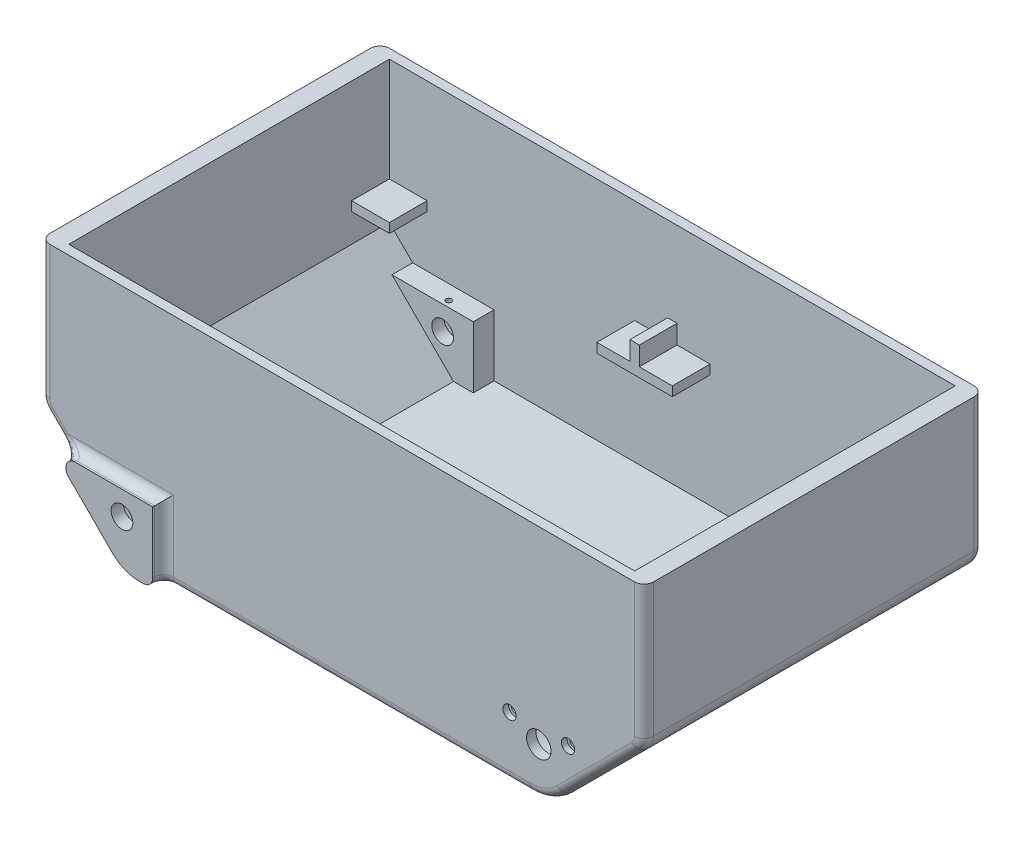
SolidWorks part; units mm, degrees
ref_plane "Front Plane" through (0, 0, 0) normal (0, 0, 1) x (1, 0, 0)
ref_plane "Top Plane" through (0, 0, 0) normal (0, 1, 0) x (1, 0, 0)
ref_plane "Right Plane" through (0, 0, 0) normal (1, 0, 0) x (0, 0, -1)
sketch "Sketch1" plane through (0, 0, 0) normal (0, 1, 0) x (1, 0, 0)
  line L1 (-160, -90) -> (160, -90)
  line L2 (-160, -90) -> (-160, 90)
  line L3 (-160, 90) -> (160, 90)
  line L4 (160, -90) -> (160, 90)
  line L5 (-160, -90) -> (160, 90) construction
  line L6 (-160, 90) -> (160, -90) construction
  point P0 (0, 0)
  dimension "D1" = 320
  dimension "D2" = 180
extrude "Boss-Extrude1" add sketch "Sketch1" along normal blind 50
sketch "Sketch2" plane through (0, 0, 90) normal (0, 0, 1) x (1, 0, 0)
  line L0 (-160, 50) -> (-110, 0)
  line L1 (-160, 0) -> (160, 0) construction
  line L2 (-110, 0) -> (-160, 0)
  line L3 (-160, 0) -> (-160, 50)
  dimension "D1" = 50
extrude "Cut-Extrude2" cut sketch "Sketch2" against normal through all
mirror "Mirror1" about plane through (0, 0, 0) normal (1, 0, 0) of "Cut-Extrude2"
ref_plane "Plane1" through (0, 0, 85) normal (0, 0, 1) x (1, 0, 0)
sketch "Sketch5" plane through (0, 0, 85) normal (0, 0, 1) x (1, 0, 0)
  line L1 (-150, 50) -> (150, 50)
  line L3 (-105, 5) -> (105, 5)
  line L5 (-160, 50) -> (160, 50) construction
  line L6 (-110, 0) -> (110, 0) construction
  line L8 (150, 50) -> (105, 5)
  line L9 (110, 0) -> (160, 50) construction
  line L10 (-150, 50) -> (-105, 5)
  line L11 (-110, 0) -> (-160, 50) construction
  dimension "D1" = 300
  dimension "D2" = 5
extrude "Cut-Extrude3" cut sketch "Sketch5" against normal blind 170
fillet "Fillet1" radius 25 2 edges at (110, 0, 0) (-110, 0, 0)
sketch "Sketch6" plane through (0, 0, -90) normal (0, 0, -1) x (-1, 0, 0)
  line L0 (102.3, 0) -> (-102.3, 0) construction
  circle A0 centre (-104.2117, 25) radius 6.5
  dimension "D1" = 13
  dimension "D2" = 25
extrude "Cut-Extrude4" cut sketch "Sketch6" against normal through all
sketch "Sketch11" plane through (0, 0, -90) normal (0, 0, -1) x (-1, 0, 0)
  circle A0 centre (-88.7117, 32) radius 2
  circle A1 centre (-104.2117, 25) radius 6.5 construction
  circle A2 centre (-119.7117, 32) radius 2
  dimension "D1" = 4
  dimension "D2" = 15.5
  dimension "D3" = 7
  dimension "D4" = 2
extrude "Cut-Extrude7" cut sketch "Sketch11" against normal through all
sketch "Sketch12" plane through (0, 0, -90) normal (0, 0, -1) x (-1, 0, 0)
  circle A0 centre (-88.7117, 32) radius 3.5
  circle A1 centre (-119.7117, 32) radius 3.5
  circle M1 centre (-88.7117, 32) radius 2
  dimension "D1" = 7
  dimension "D2" = 7
extrude "Cut-Extrude8" cut sketch "Sketch12" against normal blind 3 contours A0 M1 | A1
mirror "Mirror3" about plane through (0, 0, 0) normal (0, 0, 1) of "Cut-Extrude8"
sketch "Sketch7" plane through (0, 0, -85) normal (0, 0, 1) x (1, 0, 0)
  line L0 (88.7117, 32) -> (119.7117, 32)
  circle A0 centre (104.2117, 32) radius 17.75
  dimension "D1" = 35.5
sketch "Sketch8" plane through (0, 0, -85) normal (0, 0, 1) x (1, 0, 0)
  line L0 (134.7756, 25) -> (113.989, 4.8879)
  line L3 (113.989, 4.8879) -> (73.1131, 4.8879)
  line L4 (73.1131, 25) -> (73.1131, 4.8879)
  line L5 (104.2117, 32) -> (73.1131, 4.8879) construction
  line L6 (122.5309, 13.1526) -> (104.2117, 32) construction
  line L9 (134.7756, 25) -> (73.1131, 25)
  point P0 (104.2117, 32)
extrude "Boss-Extrude2" add sketch "Sketch8" along normal blind 170 contours L4 L3 L0 L9
extrude "Cut-Extrude11" cut sketch "Sketch7" along normal blind 170 contours A0
fillet "Fillet2" radius 25 1 edges at (125, 25, 0)
sketch "Sketch15" plane through (0, 0, -85) normal (0, 0, 1) x (1, 0, 0)
  circle A0 centre (104.2117, 32) radius 18.75
  dimension "D1" = 37.5
extrude "Cut-Extrude12" cut sketch "Sketch15" along normal blind 50 contours A0
mirror "Mirror5" about plane through (0, 0, 0) normal (0, 0, 1) of "Cut-Extrude12"
sketch "Sketch16" plane through (0, 50, 0) normal (0, 1, 0) x (1, 0, 0)
  line L1 (-160, 90) -> (160, 90)
  line L2 (-160, 90) -> (-160, -90)
  line L3 (-160, -90) -> (160, -90)
  line L4 (160, 90) -> (160, -90)
  line L9 (150, 85) -> (-150, 85)
  line L10 (150, 85) -> (150, -85)
  line L11 (150, -85) -> (-150, -85)
  line L12 (-150, 85) -> (-150, -85)
  line L13 (160, 90) -> (-160, 90)
  line L14 (160, 90) -> (160, -90)
  line L15 (160, -90) -> (-160, -90)
  line L16 (-160, 90) -> (-160, -90)
  line M1 (-150, -85) -> (-150, 85)
  line M2 (-150, 85) -> (150, 85)
  line M3 (150, 85) -> (150, -85)
  line M4 (150, -85) -> (-150, -85)
  line M5 (160, -90) -> (160, 90)
  line M6 (160, 90) -> (-160, 90)
  line M7 (-160, 90) -> (-160, -90)
  line M8 (-160, -90) -> (160, -90)
extrude "Boss-Extrude4" add sketch "Sketch16" along normal blind 75 contours M8 M5 M6 M7 M4 M1 M2 M3
fillet "Fillet3" radius 10 2 edges at (-160, 50, 0) (160, 50, 0)
ref_plane "Plane2" through (0, 65, 0) normal (0, 1, 0) x (1, 0, 0)
sketch "Sketch17" plane through (0, 65, 0) normal (0, 1, 0) x (1, 0, 0)
  line L0 (86.8174, 85) -> (73.1131, 85) construction
  line L1 (-150, 85) -> (-130, 85)
  line L2 (-150, 85) -> (-150, 65)
  line L3 (-150, 65) -> (-130, 65)
  line L4 (-130, 85) -> (-130, 65)
  line L7 (-150, 85) -> (-150, -85) construction
  point P8 (-150, 75)
  dimension "D1" = 20
  dimension "D2" = 20
extrude "Boss-Extrude5" add sketch "Sketch17" along normal blind 5
pattern_linear "LPattern1" count 2 spacing 150 along (0, 0, 1) count 2 spacing 130 along (1, 0, 0) of "Boss-Extrude5"
mirror "Mirror6" about plane through (0, 0, 0) normal (1, 0, 0) of "LPattern1", "Boss-Extrude5"
sketch "Sketch18" plane through (0, 70, 0) normal (0, 1, 0) x (1, 0, 0)
  line L1 (-2.5, 65) -> (2.5, 65)
  line L3 (-2.5, 85) -> (2.5, 85)
  line L4 (2.5, 65) -> (2.5, 85)
  line L5 (20, 85) -> (-20, 85) construction
  line L6 (-2.5, 65) -> (-2.5, 85)
extrude "Boss-Extrude6" add sketch "Sketch18" along normal blind 10
mirror "Mirror7" about plane through (0, 0, 0) normal (0, 0, 1) of "Boss-Extrude6"
ref_plane "Plane3" through (160, 125, 90) normal (1, 0, 0) x (0, 0, -1)
ref_plane "Plane6" through (0, 0, 74) normal (0, 0, -1) x (-1, 0, 0)
sketch "Sketch34" plane through (0, 0, 74) normal (0, 0, -1) x (-1, 0, 0)
  line L0 (99.6447, 0) -> (-99.6447, 0) construction
  line L8 (94.5263, 37.67) -> (147.67, 37.67)
  line L9 (94.5263, 37.67) -> (94.5263, 0)
  line L10 (94.5263, 0) -> (110, 0)
  line L12 (147.67, 37.67) -> (110, 0)
  line L13 (117.3223, 7.3223) -> (157.0711, 47.0711) construction
  point P1 (144.7126, 34.7126)
  point P2 (0, 0)
  point P6 (147.67, 37.67)
  point P11 (0, 0)
  point P12 (0, 0)
  point P13 (110, 0)
  point P14 (89.4739, 0)
  point P15 (94.5263, 0)
extrude "Boss-Extrude10" add sketch "Sketch34" against normal blind 22
sketch "Sketch38" plane through (0, 37.67, 0) normal (0, 1, 0) x (1, 0, 0)
  line L0 (160, -90) -> (160, 90) construction
  line L1 (-137.67, -74) -> (-94.5263, -74) construction
  circle A0 centre (-110.7883, -77.25) radius 1.5
  dimension "D1" = 3
  dimension "D2" = 270.7883
  dimension "D3" = 3.25
extrude "Cut-Extrude30" cut sketch "Sketch38" against normal blind 8
sketch "Sketch39" plane through (0, 0, 74) normal (0, 0, -1) x (-1, 0, 0)
  line L0 (-104.2117, 25) -> (122.1721, 25) construction
  circle A0 centre (110.7883, 25) radius 5.75
  circle A1 centre (-104.2117, 25) radius 6.5 construction
  dimension "D1" = 11.5
  dimension "D2" = 215
extrude "Cut-Extrude31" cut sketch "Sketch39" against normal blind 6.5
sketch "Sketch40" plane through (0, 0, 80.5) normal (0, 0, -1) x (-1, 0, 0)
  circle A0 centre (110.7883, 25) radius 2.25
  dimension "D1" = 4.5
extrude "Cut-Extrude32" cut sketch "Sketch40" against normal through all
sketch "Sketch41" plane through (0, 0, 96) normal (0, 0, 1) x (1, 0, 0)
  circle A0 centre (-110.7883, 25) radius 5.75
  circle A1 centre (-110.7883, 25) radius 2.25 construction
  dimension "D1" = 11.5
extrude "Cut-Extrude33" cut sketch "Sketch41" against normal blind 6.5
mirror "Mirror14" about plane through (0, 0, 0) normal (0, 0, 1) of "Cut-Extrude33", "Cut-Extrude32", "Cut-Extrude31", "Cut-Extrude30", "Boss-Extrude10"
fillet "Fillet8" radius 20 2 edges at (-110, 0, -85) (-110, 0, 85)
fillet "Fillet9" radius 5 2 edges at (-94.5263, 18.835, -90) (-121.0982, 37.67, -90)
fillet "Fillet10" radius 5 2 edges at (-94.5263, 18.835, 90) (-121.0982, 37.67, 90)
fillet "Fillet11" radius 5 10 edges at (-160, 89.5711, 90) (-160, 89.5711, -90) (-159.2388, 50.3153, -90) (-159.2388, 50.3153, 90) (-147.67, 37.67, 95.5) (-147.67, 37.67, -95.5) (-154.8706, 44.8706, -90) (-149.1345, 39.1345, -91.4645) (-154.8706, 44.8706, 90) (-149.1345, 39.1345, 91.4645)
fillet "Fillet12" radius 5 14 edges at (160, 89.5711, 90) (160, 89.5711, -90) (159.2388, 50.3153, -90) (159.2388, 50.3153, 90) (-94.5263, 0, 95.5) (5.0592, 0, -90) (137.1967, 27.1967, 90) (109.2117, 1.903, 90) (137.1967, 27.1967, -90) (-94.5263, 0, -95.5) (109.2117, 1.903, -90) (-93.0618, 0, -91.4645) (5.0592, 0, 90) (-93.0618, 0, 91.4645)
